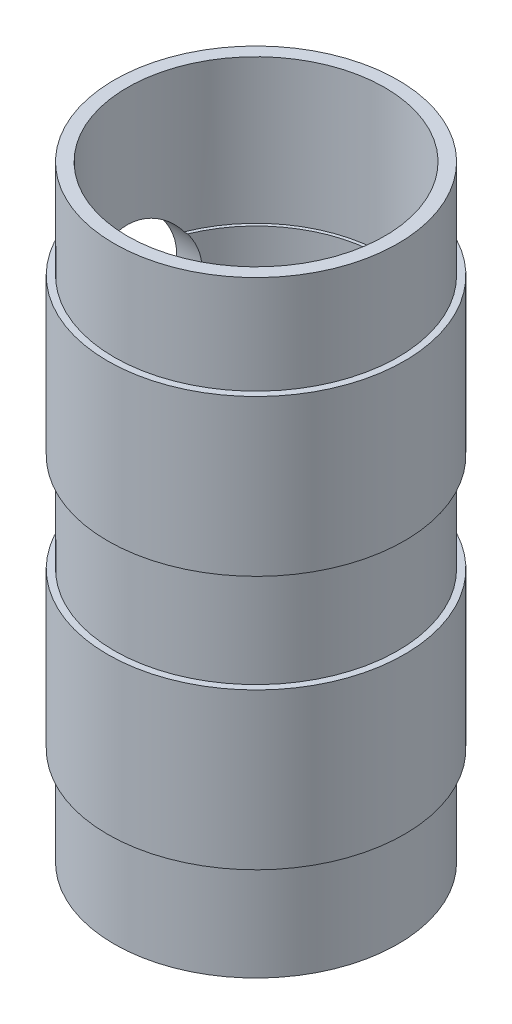
SolidWorks part; units mm, degrees
ref_plane "Front Plane" through (0, 0, 0) normal (0, 0, 1) x (1, 0, 0)
ref_plane "Top Plane" through (0, 0, 0) normal (0, 1, 0) x (1, 0, 0)
ref_plane "Right Plane" through (0, 0, 0) normal (1, 0, 0) x (0, 0, -1)
sketch "Sketch1" plane through (0, 0, 0) normal (0, 1, 0) x (1, 0, 0)
  line L0 (0, 38.25) -> (0, 45.25) construction
  circle A0 centre (0, 0) radius 38.25
  circle A1 centre (0, 0) radius 45.25
  dimension "D1" = 76.5
  dimension "D2" = 7
extrude "Boss-Extrude1" add sketch "Sketch1" along normal mid plane 185
sketch "Sketch2" plane through (0, -92.5, 0) normal (0, -1, 0) x (1, 0, 0)
  line L0 (0, 36.25) -> (0, 38.25) construction
  circle A0 centre (0, 0) radius 36.25
  circle A1 centre (0, 0) radius 38.25 construction
  circle A2 centre (0, 0) radius 38.25
  dimension "D1" = 2
extrude "Boss-Extrude2" add sketch "Sketch2" against normal blind 100 from offset 6.35 offset against normal yes
sketch "Sketch6" plane through (0, 92.5, 0) normal (0, 1, 0) x (1, 0, 0)
  line L0 (0, 38.25) -> (0, 39.25) construction
  circle A0 centre (0, 0) radius 39.25
  circle A1 centre (0, 0) radius 38.25 construction
  circle A2 centre (0, 0) radius 38.25
  dimension "D1" = 1
extrude "Cut-Extrude3" cut sketch "Sketch6" against normal blind 44
sketch "Sketch7" plane through (0, 0, 0) normal (1, 0, 0) x (0, 0, -1)
  line L0 (45.25, 92.5) -> (-45.25, 92.5) construction
  circle A0 centre (0, 38.75) radius 17.5
  dimension "D2" = 35
  dimension "D1" = 53.75
extrude "Cut-Extrude4" cut sketch "Sketch7" against normal through all
sketch "Sketch8" plane through (0, 92.5, 0) normal (0, 1, 0) x (1, 0, 0)
  line L0 (0, 43.25) -> (0, 45.25) construction
  circle A0 centre (0, 0) radius 45.25 construction
  circle A1 centre (0, 0) radius 45.25
  circle A2 centre (0, 0) radius 43.25
  dimension "D1" = 2
extrude "Cut-Extrude5" cut sketch "Sketch8" against normal blind 30
mirror "Mirror1" about plane through (0, 0, 0) normal (0, 1, 0) of "Cut-Extrude5"
sketch "Sketch9" plane through (0, 0, 0) normal (0, 1, 0) x (1, 0, 0)
  circle A1 centre (0, 0) radius 43.25
  circle A2 centre (0, 0) radius 43.25
  circle A3 centre (0, 0) radius 45.25
  circle A4 centre (0, 0) radius 45.25
  dimension "D1" = 0
  dimension "D2" = 0
extrude "Cut-Extrude6" cut sketch "Sketch9" against normal mid plane 30
